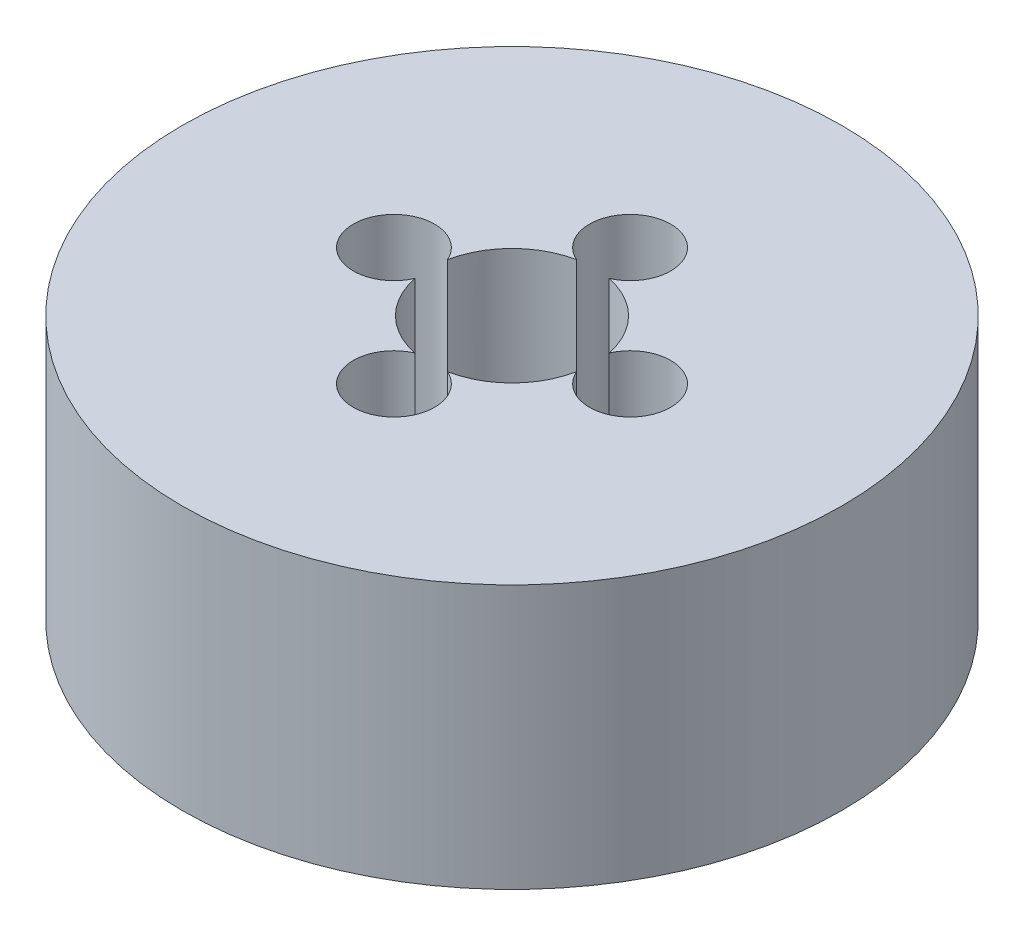
SolidWorks part; units mm, degrees
ref_plane "Front Plane" through (0, 0, 0) normal (0, 0, 1) x (1, 0, 0)
ref_plane "Top Plane" through (0, 0, 0) normal (0, 1, 0) x (1, 0, 0)
ref_plane "Right Plane" through (0, 0, 0) normal (1, 0, 0) x (0, 0, -1)
sketch "Sketch1" plane through (0, 0, 0) normal (0, 1, 0) x (1, 0, 0)
  circle A0 centre (0, 0) radius 20
  dimension "FLANGE_OD" = 40
extrude "Boss-Extrude1" add sketch "Sketch1" along normal blind 16
sketch "Sketch2" plane through (0, 0, 0) normal (0, 1, 0) x (1, 0, 0)
  circle A0 centre (0, 0) radius 5
  dimension "BORE_D" = 10
extrude "Cut-Extrude1" cut sketch "Sketch2" along normal through all
sketch "Sketch3" plane through (0, 16, 0) normal (0, 1, 0) x (1, 0, 0)
  circle A0 centre (0, 0) radius 7.1626 construction
  circle A1 centre (-7.1626, 0) radius 2.4655
  dimension "BOLT_D" = 4.931
  dimension "BOLT_PCD" = 14.3253
extrude "Cut-Extrude2" cut sketch "Sketch3" against normal blind 12.3965
pattern_circular "CirPattern1" count 4 over 360 about axis through (0, 0, 0) along (0, 1, 0) of "Cut-Extrude2"
